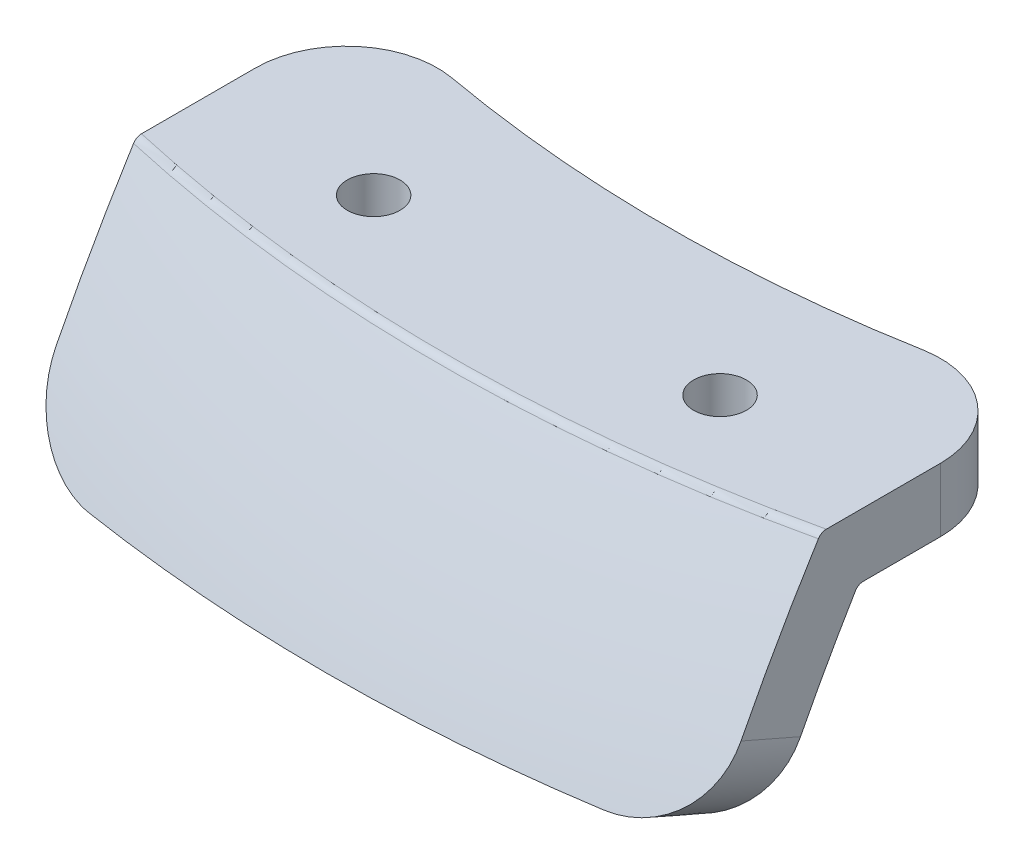
SolidWorks part; units mm, degrees
material "Polyether Polyol"
ref_plane "Front Plane" through (0, 0, 0) normal (0, 0, 1) x (1, 0, 0)
ref_plane "Top Plane" through (0, 0, 0) normal (0, 1, 0) x (1, 0, 0)
ref_plane "Right Plane" through (0, 0, 0) normal (1, 0, 0) x (0, 0, -1)
sketch "Sketch1" plane through (0, 0, 0) normal (1, 0, 0) x (0, 0, -1)
  line L0 (-182.9297, 172.8317) -> (-176.5279, 170.0001) construction
  line L1 (-170.3849, 196.7005) -> (-145.5262, 196.7005) construction
  line L9 (-145.5262, 196.7005) -> (-145.5262, 189.7005) construction
  line L10 (-145.5262, 189.7005) -> (-166.4259, 189.7005) construction
  line L11 (-182.9297, 172.8317) -> (-176.5279, 170.0001)
  line L12 (-170.3849, 196.7005) -> (-145.5262, 196.7005)
  line L13 (-145.5262, 196.7005) -> (-145.5262, 189.7005)
  line L14 (-145.5262, 189.7005) -> (-166.4259, 189.7005)
  line L15 (0, 0) -> (0, 91.9198) construction
  arc A5 (-166.4259, 189.7005) -> (-176.5279, 170.0001) centre (0, 91.9198) ccw construction
  arc A6 (-170.3849, 196.7005) -> (-182.9297, 172.8317) centre (0, 91.9198) ccw construction
  arc A7 (-166.4259, 189.7005) -> (-176.5279, 170.0001) centre (0, 91.9198) ccw
  arc A8 (-170.3849, 196.7005) -> (-182.9297, 172.8317) centre (0, 91.9198) ccw
revolve "Revolve1" add sketch "Sketch1" angle 30 mid plane about L15
sketch "Sketch2" plane through (0, 0, 0) normal (-1, 0, 0) x (0, 0, 1)
  line L0 (0, 91.9198) -> (171.9865, 179.5513) construction
  line L3 (0, -200000) -> (0, 218797.9879) construction
  arc A0 (176.5279, 170.0001) -> (166.4259, 189.7005) centre (0, 91.9198) ccw construction
  dimension "D1" = 63
ref_plane "Plane1" through (0, 72.9744, -37.1823) normal (0, -0.891, 0.454) x (0, 0.454, 0.891)
sketch "Sketch4" plane through (0, 72.9744, -37.1823) normal (0, -0.891, 0.454) x (0, 0.454, 0.891)
  line L0 (219.8801, 19.237) -> (239.1484, 20.9228) construction
  line L1 (219.7494, 20.7313) -> (239.0177, 22.4171)
  line L2 (219.7494, 20.7313) -> (219.8801, 19.237)
  line L3 (41.7307, 0) -> (234.7557, 0) construction
  line L4 (219.8801, 19.237) -> (239.1484, 20.9228)
  line L5 (239.0177, 22.4171) -> (239.1484, 20.9228)
  dimension "D1" = 3
  dimension "D2" = 5
revolve "Cut-Revolve1" cut sketch "Sketch4" angle 360 about L0
mirror "Mirror1" about plane through (0, 0, 0) normal (1, 0, 0) of "Cut-Revolve1"
sketch "Sketch5" plane through (0, 0, 0) normal (0, 1, 0) x (1, 0, 0)
  line L1 (37.665, -140.5675) -> (-37.665, -140.5675)
  line L2 (37.665, -140.5675) -> (37.665, -182.9297)
  line L3 (37.665, -182.9297) -> (-37.665, -182.9297)
  line L4 (-37.665, -140.5675) -> (-37.665, -182.9297)
  arc A0 (-47.3457, -176.6965) -> (47.3457, -176.6965) centre (0, 0) ccw construction
extrude "Cut-Extrude2" cut sketch "Sketch5" along normal through all flip side to cut
fillet "Fillet1" radius 10 4 edges at (-37.665, 193.2005, 140.5675) (37.665, 193.2005, 140.5675)
fillet "Fillet2" radius 1 2 edges at (0, 196.7005, 170.3849) (0, 189.7005, 166.4259)
sketch "Sketch6" plane through (0, 196.7005, 0) normal (0, 1, 0) x (1, 0, 0)
  circle A0 centre (19.05, -158.6742) radius 2.9 construction
  circle A1 centre (-19.05, -158.6742) radius 2.9 construction
  circle A2 centre (19.05, -158.6742) radius 2.9
  circle A3 centre (-19.05, -158.6742) radius 2.9
extrude "Cut-Extrude3" cut sketch "Sketch6" against normal through all
